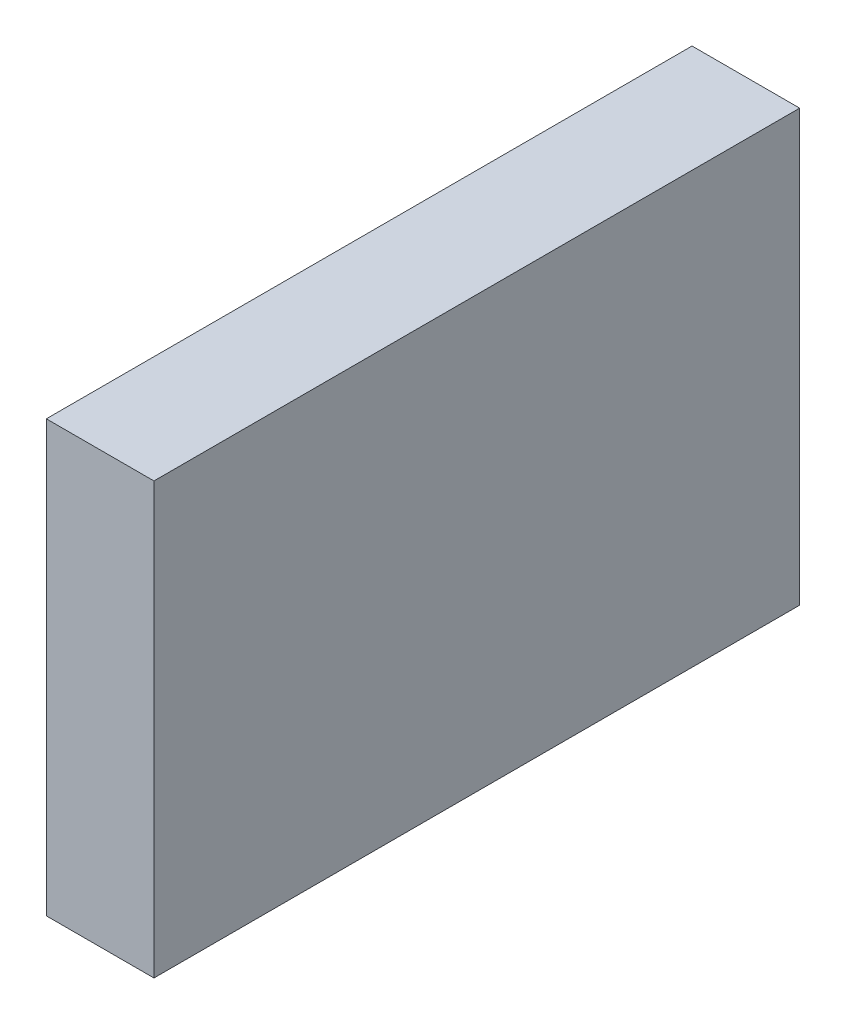
SolidWorks part; units mm, degrees
ref_plane "Front Plane" through (0, 0, 0) normal (0, 0, 1) x (1, 0, 0)
ref_plane "Top Plane" through (0, 0, 0) normal (0, 1, 0) x (1, 0, 0)
ref_plane "Right Plane" through (0, 0, 0) normal (1, 0, 0) x (0, 0, -1)
sketch "Sketch1" plane through (0, 0, 0) normal (0, 0, 1) x (1, 0, 0)
  line L0 (0, 0) -> (0, 76.2)
  line L5 (0, 76.2) -> (88.098, 76.2)
  line L6 (88.098, 76.2) -> (88.098, 101.6)
  line L7 (0, 0) -> (6.35, 0)
  line L8 (6.35, 0) -> (6.35, 76.2)
  line L9 (6.35, 76.2) -> (6.35, 69.85)
  line L10 (6.35, 69.85) -> (101.1141, 69.85)
  line L11 (88.098, 101.6) -> (94.448, 101.6)
  line L12 (94.448, 101.6) -> (94.448, 69.85)
  dimension "D1" = 25.4
  dimension "D2" = 76.2
extrude "Boss-Extrude1" add sketch "Sketch1" along normal blind 38.1 contours L7 L8 L5 L0 | L12 L11 L6 L5 L8 L10 region at (3.175, 38.1, 0) region at (47.224, 75.2636, 0)
sketch "Sketch2" plane through (0, 0, 0) normal (-1, 0, 0) x (0, 0, 1)
  line L0 (19.05, 20.32) -> (19.05, 42.672)
  line L1 (0, 0) -> (0, 76.2) construction
  line L2 (38.1, 0) -> (0, 0)
  line L3 (38.1, 0) -> (38.1, 50.8)
  line L4 (38.1, 50.8) -> (0, 50.8)
  line L5 (0, 0) -> (0, 50.8)
  line L6 (38.1, 0) -> (38.1, 20.32)
  line L7 (38.1, 20.32) -> (0, 20.32)
  circle A0 centre (19.05, 20.32) radius 11.049
  circle A1 centre (19.05, 42.672) radius 3.556
  point P13 (19.05, 20.32)
  dimension "D1" = 22.352
  dimension "D2" = 20.32
extrude "Cut-Extrude1" cut sketch "Sketch2" against normal blind 6.35 contours A0
extrude "Cut-Extrude2" cut sketch "Sketch2<4>" against normal blind 6.35 contours A1
sketch "Sketch2<4>" plane through (0, 0, 0) normal (-1, 0, 0) x (0, 0, 1) same geometry as "Sketch2"
sketch "Sketch4" plane through (0, 0, 38.1) normal (0, 0, 1) x (1, 0, 0)
  line L1 (0, 76.2) -> (111.3465, 76.2)
  line L2 (0, 76.2) -> (0, -7.1162)
  line L3 (0, -7.1162) -> (111.3465, -7.1162)
  line L4 (111.3465, 76.2) -> (111.3465, -7.1162)
extrude "Cut-Extrude3" cut sketch "Sketch4" against normal blind 76.2
